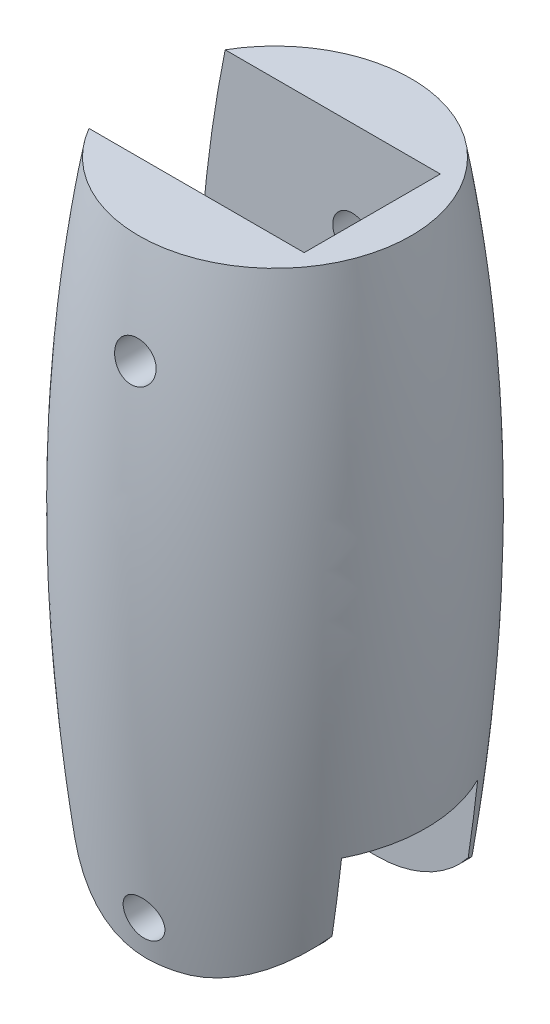
SolidWorks part; units mm, degrees
ref_plane "Front Plane" through (0, 0, 0) normal (0, 0, 1) x (1, 0, 0)
ref_plane "Top Plane" through (0, 0, 0) normal (0, 1, 0) x (1, 0, 0)
ref_plane "Right Plane" through (0, 0, 0) normal (1, 0, 0) x (0, 0, -1)
sketch "Sketch1" plane through (0, 0, 0) normal (1, 0, 0) x (0, 0, -1)
  line L0 (0, 16) -> (0, -16)
  line L1 (0, 16) -> (7, 16)
  line L2 (0, -16) -> (7, -16)
  line L3 (12.2094, -13.5442) -> (1.7906, 45.5442) construction
  spline S0 degree 2 poles (7, 16) (9.6047, 1.2279) (7, -16) knots 0 0 0 1 1 1
  point P3 (0, 0)
  dimension "D3" = 100
  dimension "D4" = 30
  dimension "D1" = 32
  dimension "D2" = 7
revolve "Revolve1" add sketch "Sketch1" angle 360 about L0
sketch "Sketch2" plane through (0, 0, 0) normal (1, 0, 0) x (0, 0, -1)
  line L0 (7, 16) -> (-7, 16) construction
  line L1 (-3.5, 5) -> (3.5, 5)
  line L2 (-3.5, 5) -> (-3.5, 16)
  line L3 (-3.5, 16) -> (3.5, 16)
  line L4 (3.5, 5) -> (3.5, 16)
  line L5 (-7, -16) -> (7, -16) construction
  line L6 (-3.5, -16) -> (3.5, -16)
  line L7 (-3.5, -16) -> (-3.5, -3)
  line L8 (-3.5, -3) -> (3.5, -3)
  line L9 (3.5, -16) -> (3.5, -3)
  point P12 (0, -3)
  point P14 (0, 5)
  dimension "D1" = 7
  dimension "D2" = 13
  dimension "D3" = 11
extrude "Cut-Extrude1" cut sketch "Sketch2" against normal through all and the other way blind 5
sketch "Sketch3" plane through (0, 0, 0) normal (0, 0, 1) x (1, 0, 0)
  line L0 (0.4689, -16) -> (0.4689, -14) construction
  line L1 (-6.0622, -16) -> (7, -16) construction
  line L2 (0.4689, 16) -> (0.4689, 11) construction
  line L3 (7, 16) -> (-6.0622, 16) construction
  circle A0 centre (0.4689, 11) radius 1
  circle A1 centre (0.4689, -14) radius 1
  dimension "D3" = 2
  dimension "D1" = 2
  dimension "D2" = 5
extrude "Cut-Extrude2" cut sketch "Sketch3" against normal through all and the other way through all
sketch "Sketch5" plane through (0, 0, 0) normal (0, 0, 1) x (1, 0, 0)
  line L6 (7, 16) -> (-6.0622, 16) construction
  line L7 (-6.0622, -16) -> (7, -16) construction
  line L8 (7, 16) -> (-6.0622, 16)
  line L9 (-6.0622, -16) -> (7, -16)
  arc A0 (1.799, 16) -> (7.7629, 10.6573) centre (1.799, 10) cw
  arc A1 (7.6915, -10.632) -> (1.7249, -16) centre (1.7249, -10) cw
  arc A2 (-7.05, -8.7976) -> (0.9101, -16) centre (0.9101, -8) ccw
  spline S6 degree 3 poles (3948.3851, -692.871) (-14.0794, -71.3135) (2.8084, -44.3747) (7.0808, -15.4586) (7.1463, -15.0087) (7.2906, -13.9869) (7.5135, -12.2671) (7.7794, -9.8719) (8.0186, -7.1591) (8.1958, -4.2936) (8.2958, -1.3905) (8.3128, 1.4682) (8.2455, 4.3093) (8.0991, 7.0399) (7.8769, 9.6911) (7.5984, 12.1339) (7.3521, 13.8603) (7.1899, 14.88) (7.1272, 15.2601) (7.077, 15.5565) (3.0772, 38.828) (-13.7046, 59.7983) (3934.4852, 770.8765) knots -2.702737 -2.702737 -2.702737 -2.702737 0.008524 0.017035 0.025535 0.050959 0.113349 0.1874 0.275886 0.367511 0.455348 0.54699 0.634319 0.720573 0.802196 0.88261 0.950037 0.964949 0.978986 0.985996 0.993001 3.182948 3.182948 3.182948 3.182948 only from (7, -16) to (7, 16) construction
  spline S7 degree 3 poles (7, -16) (7.0136, -15.9097) (7.0408, -15.7292) (7.0808, -15.4586) (7.1463, -15.0087) (7.2906, -13.9869) (7.5135, -12.2671) (7.7794, -9.8719) (8.0186, -7.1591) (8.1958, -4.2936) (8.2958, -1.3905) (8.3128, 1.4682) (8.2455, 4.3093) (8.0991, 7.0399) (7.8769, 9.6911) (7.5984, 12.1339) (7.3521, 13.8603) (7.1899, 14.88) (7.1272, 15.2601) (7.077, 15.5565) (7.0389, 15.7784) (7.013, 15.9261) (7, 16) knots 0 0 0 0 0.008524 0.017035 0.025535 0.050959 0.113349 0.1874 0.275886 0.367511 0.455348 0.54699 0.634319 0.720573 0.802196 0.88261 0.950037 0.964949 0.978986 0.985996 0.993001 1 1 1 1
  spline S8 degree 3 poles (3957.138, -280.9247) (834.6244, -383.6356) (17.7265, -239.0621) (-25.6356, 163.8871) (409.7296, 385.9929) (3861.4248, 931.6094) knots -52.472554 -52.472554 -52.472554 -52.472554 0.5 0.5 40.519248 40.519248 40.519248 40.519248 only from (-6.0622, -16) to (-7.4565, -3) construction
  spline S9 degree 3 poles (-6.0622, -16) (-6.4378, -13.8487) (-6.7415, -11.6897) (-7.2078, -7.3565) (-7.3701, -5.1823) (-7.4565, -3) knots 0 0 0 0 0.5 0.5 1 1 1 1
  dimension "D1" = 6
  dimension "D2" = 8
extrude "Cut-Extrude4" cut sketch "Sketch5" against normal blind 20 from offset 10 contours L9 S7 A1 | S9 L9 A2 region at (-4.7972, -14.427, 0) region at (6.0155, -14.825, 0) body kept at (0.9101, -16, -6.9406)
sketch "Sketch6" plane through (0, 5, 0) normal (0, 1, 0) x (1, 0, 0)
  circle A0 centre (4, 0) radius 0.5
  circle A1 centre (-3, 0) radius 0.5
  dimension "D1" = 1
  dimension "D2" = 1
  dimension "D3" = 4
  dimension "D4" = 3
extrude "Cut-Extrude5" cut sketch "Sketch6" against normal through all
sketch "Sketch7" plane through (5, 0, 0) normal (-1, 0, 0) x (0, 0, 1)
  line L0 (3.5, -8.7976) -> (3.5, -16) construction
  line L1 (-3.5, -16) -> (3.5, -16)
  line L2 (-3.5, -16) -> (-3.5, -10)
  line L3 (-3.5, -10) -> (3.5, -10)
  line L4 (3.5, -16) -> (3.5, -10)
  dimension "D1" = 6
extrude "Cut-Extrude6" cut sketch "Sketch7" against normal through all
